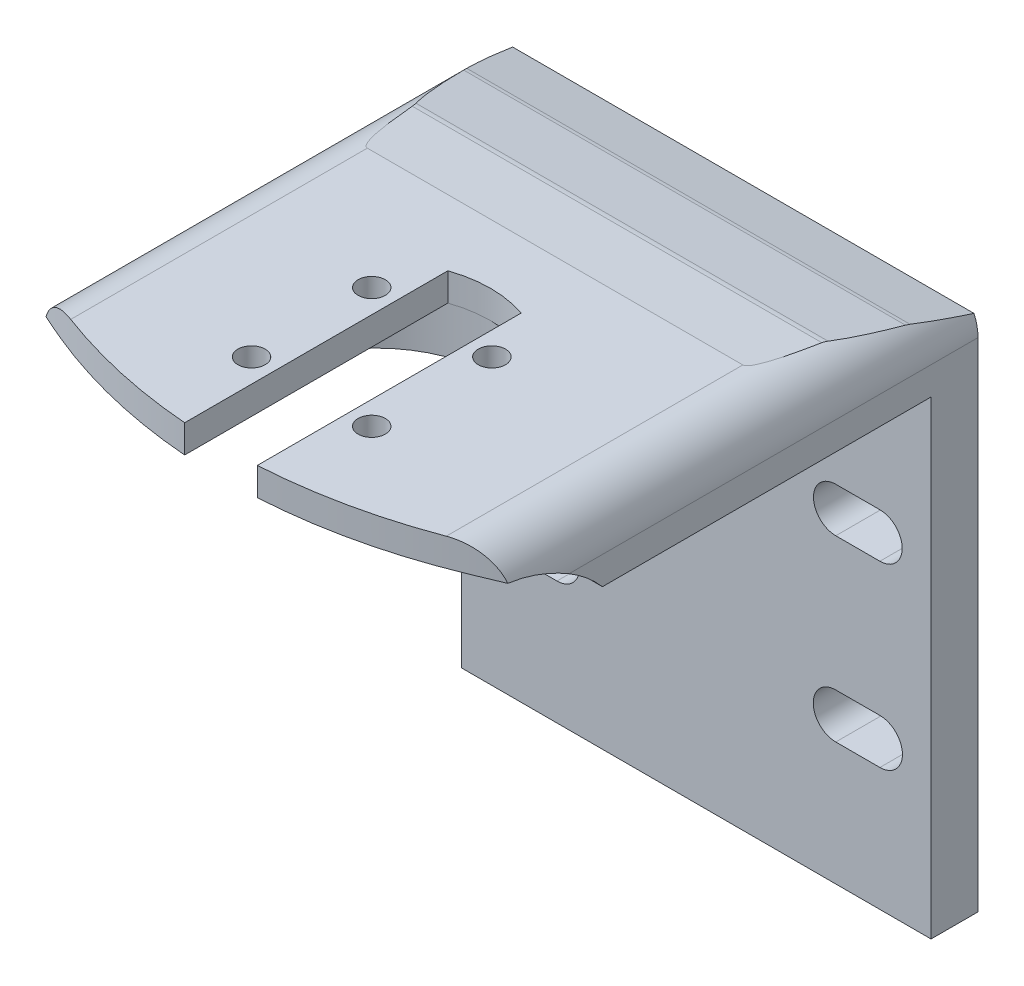
SolidWorks part; units mm, degrees
ref_plane "Front Plane" through (0, 0, 0) normal (0, 0, 1) x (1, 0, 0)
ref_plane "Top Plane" through (0, 0, 0) normal (0, 1, 0) x (1, 0, 0)
ref_plane "Right Plane" through (0, 0, 0) normal (1, 0, 0) x (0, 0, -1)
sketch "Sketch2" plane through (0, 0, 0) normal (0, 0, 1) x (1, 0, 0)
  line L0 (19.2481, 9.5) -> (23.9481, 9.5) construction
  line L1 (-20.6019, -25) -> (29.3981, -25)
  line L2 (-20.6019, -25) -> (-20.6019, 25)
  line L3 (-20.6019, 25) -> (29.3981, 25)
  line L4 (29.3981, -25) -> (29.3981, 25)
  line L7 (19.2481, 11.875) -> (23.9481, 11.875)
  line L8 (19.2481, 7.125) -> (23.9481, 7.125)
  line L9 (-15.1519, 9.5) -> (-10.4519, 9.5) construction
  line L10 (-15.1519, 11.9) -> (-10.4519, 11.9)
  line L11 (-15.1519, 7.1) -> (-10.4519, 7.1)
  line L12 (19.2481, -9.5) -> (23.9481, -9.5) construction
  line L13 (19.2481, -7.1) -> (23.9481, -7.1)
  line L14 (19.2481, -11.9) -> (23.9481, -11.9)
  line L15 (-15.1519, -9.5) -> (-10.4519, -9.5) construction
  line L16 (-15.1519, -7.1) -> (-10.4519, -7.1)
  line L17 (-15.1519, -11.9) -> (-10.4519, -11.9)
  arc A0 (19.2481, 11.875) -> (19.2481, 7.125) centre (19.2481, 9.5) ccw
  arc A1 (23.9481, 7.125) -> (23.9481, 11.875) centre (23.9481, 9.5) ccw
  arc A2 (-15.1519, 11.9) -> (-15.1519, 7.1) centre (-15.1519, 9.5) ccw
  arc A3 (-10.4519, 7.1) -> (-10.4519, 11.9) centre (-10.4519, 9.5) ccw
  arc A4 (19.2481, -7.1) -> (19.2481, -11.9) centre (19.2481, -9.5) ccw
  arc A5 (23.9481, -11.9) -> (23.9481, -7.1) centre (23.9481, -9.5) ccw
  arc A6 (-15.1519, -7.1) -> (-15.1519, -11.9) centre (-15.1519, -9.5) ccw
  arc A7 (-10.4519, -11.9) -> (-10.4519, -7.1) centre (-10.4519, -9.5) ccw
  point P0 (0, 0)
  point P8 (21.5981, 9.5)
  point P15 (-12.8019, 9.5)
  point P20 (21.5981, -9.5)
  point P27 (-12.8019, -9.5)
  point P34 (-12.8019, 11.9)
  dimension "D3" = 4.7
  dimension "D1" = 50
  dimension "D2" = 50
  dimension "D4" = 4.75
  dimension "D5" = 15.5
  dimension "D6" = 4.8
  dimension "D7" = 4.7
  dimension "D8" = 34.4
  dimension "D9" = 4.7
  dimension "D10" = 4.8
  dimension "D11" = 4.7
  dimension "D12" = 4.8
  dimension "D13" = 34.4
  dimension "D14" = 15.5
  dimension "D15" = 15.5
  dimension "D16" = 7.8
  dimension "D17" = 7.8
extrude "Boss-Extrude1" add sketch "Sketch2" along normal blind 5
sketch "Sketch3" plane through (0, 25, 0) normal (0, 1, 0) x (1, 0, 0)
  line L1 (-20.6019, 0) -> (29.3981, 0)
  line L2 (-20.6019, 0) -> (-20.6019, -40)
  line L4 (29.3981, 0) -> (29.3981, -40)
  line L8 (-20.6019, -40) -> (-8.4019, -40)
  line L9 (29.3981, -40) -> (17.1981, -40)
  arc A2 (-8.4019, -40) -> (17.1981, -40) centre (4.3981, -39.1234) cw
  dimension "D2" = 50
  dimension "D3" = 12.2
  dimension "D1" = 40
  dimension "D4" = 12.2
extrude "Boss-Extrude2" add sketch "Sketch3" along normal blind 5
sketch "Sketch6" plane through (29.3981, 0, 0) normal (1, 0, 0) x (0, 0, -1)
  line L3 (-20.0485, 32.9795) -> (-13.179, 32.6251)
  line L4 (-13.179, 32.6251) -> (-6.0528, 31.4897)
  line L5 (-6.0528, 31.4897) -> (0, 30)
  line L6 (-58.497, 30) -> (-58.497, 32.9795)
  line L7 (-58.497, 32.9795) -> (-20.0485, 32.9795)
  line L8 (-58.497, 30) -> (0, 30)
extrude "Boss-Extrude39" add sketch "Sketch6" against normal blind 50
sketch "Sketch7" plane through (0, 30, 0) normal (0, -1, 0) x (1, 0, 0)
  line L5 (-20.6019, 58.497) -> (29.3981, 58.497) construction
  line L7 (0, 27.0708) -> (0, 58.497)
  line L8 (0, 58.497) -> (7.805, 58.497)
  line L9 (7.805, 27.0708) -> (7.805, 58.497)
  line L10 (-20.6019, 58.497) -> (-20.6019, 40) construction
  line L11 (-20.6019, 49.2485) -> (29.3981, 49.2485)
  line L12 (29.3981, 58.497) -> (29.3981, 40) construction
  arc A0 (-8.4019, 40) -> (17.1981, 40) centre (4.3981, 39.1234) ccw construction
  arc A1 (0, 27.0708) -> (7.805, 27.0708) centre (3.9025, 38.3443) ccw
  arc A2 (-20.6019, 49.2485) -> (0, 58.497) centre (0.976, 28.7522) cw
  arc A3 (7.805, 58.497) -> (29.3981, 49.2485) centre (7.8186, 28.697) cw
  line M5 (-20.6019, 58.497) -> (-20.6019, 40)
  line M9 (29.3981, 40) -> (29.3981, 58.497)
  line M10 (29.3981, 58.497) -> (-20.6019, 58.497)
  dimension "D1" = 29.7608
  dimension "D2" = 29.8
extrude "Cut-Extrude2" cut sketch "Sketch7" against normal through all both and the other way through all contours L7 L11 L9 M10 | L7 A1 L9 L11 | A3 M10 M9 | A2 M5 M10 region at (24.185, 30, 55.8159) region at (3.9025, 30, 37.9388) region at (3.9025, 30, 53.8727) region at (-15.4184, 30, 55.813)
fillet "Fillet5" radius 5 2 edges at (29.3981, 32.9795, 34.6485) (-20.6019, 32.9795, 34.6485)
fillet "Fillet6" radius 5 2 edges at (4.3981, 32.6251, 13.179) (4.3981, 31.4897, 6.0528)
sketch "Sketch8" plane through (0, 30, 0) normal (0, -1, 0) x (1, 0, 0)
  circle A1 centre (-2.5089, 45.4734) radius 1.45
  circle A2 centre (10.2911, 45.4734) radius 1.45
  circle A3 centre (-2.5089, 32.6734) radius 1.45
  circle A4 centre (10.2911, 32.6734) radius 1.45
  dimension "D1" = 2.9
  dimension "D2" = 2.9
  dimension "D3" = 2.9
  dimension "D4" = 2.9
  dimension "D9" = 12.8
  dimension "D10" = 12.8
extrude "Cut-Extrude3" cut sketch "Sketch8" along normal through all both and the other way through all
sketch "Sketch9" plane through (0, 32.9795, 0) normal (0, 1, 0) x (1, 0, 0)
  arc A0 (-20.1755, -49.6883) -> (28.9716, -49.6872) centre (4.3969, 1.5513) ccw
  arc A1 (-20.1755, -49.6883) -> (28.9716, -49.6872) centre (4.3981, -49.6877) ccw
extrude "Cut-Extrude6" cut sketch "Sketch9" against normal through all both and the other way through all
fillet "Fillet7" radius 14.5 2 edges at (-14.2887, 30, 40) (23.0849, 30, 40)
